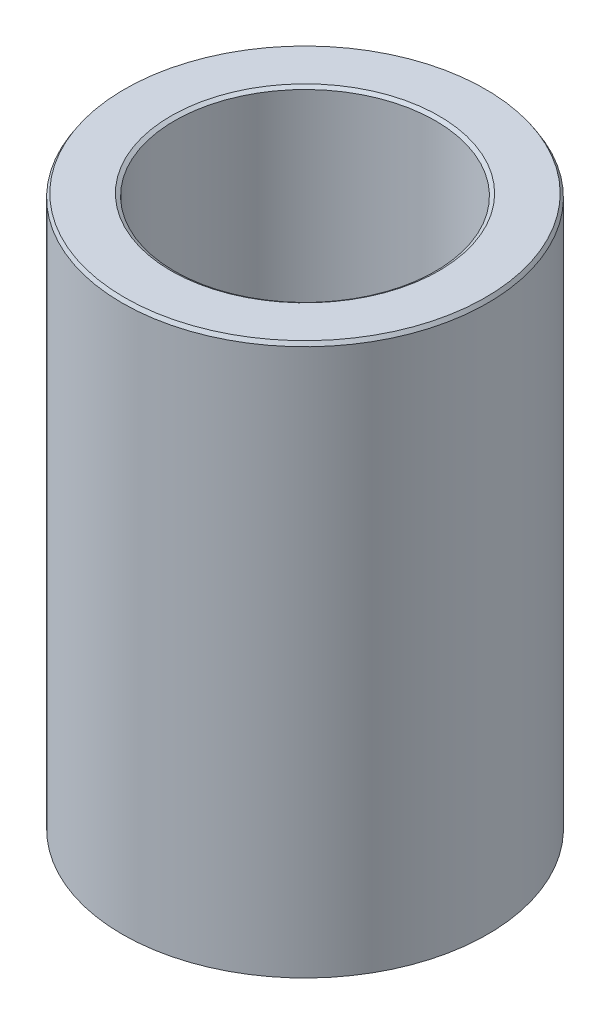
SolidWorks part; units mm, degrees
ref_plane "Front Plane" through (0, 0, 0) normal (0, 0, 1) x (1, 0, 0)
ref_plane "Top Plane" through (0, 0, 0) normal (0, 1, 0) x (1, 0, 0)
ref_plane "Right Plane" through (0, 0, 0) normal (1, 0, 0) x (0, 0, -1)
sketch "Sketch1" plane through (0, 0, 0) normal (0, 1, 0) x (1, 0, 0)
  circle A0 centre (0, 0) radius 35
  dimension "SLEEVE_OD" = 70
extrude "Boss-Extrude1" add sketch "Sketch1" along normal blind 105.8344
sketch "Sketch2" plane through (0, 0, 0) normal (0, 1, 0) x (1, 0, 0)
  circle A0 centre (0, 0) radius 24.9798
  dimension "BORE_D" = 49.9596
extrude "Cut-Extrude1" cut sketch "Sketch2" along normal through all
chamfer "Chamfer1" distance 0.7011 angle 32.114 4 edges at (0, 105.8344, 24.9798) (0, 0, 24.9798) (0, 0, 35) (0, 105.8344, 35) first distance on face at (0, 105.8344, 24.9798) first distance on face at (0, 0, 24.9798) first distance on face at (0, 105.8344, 35)
